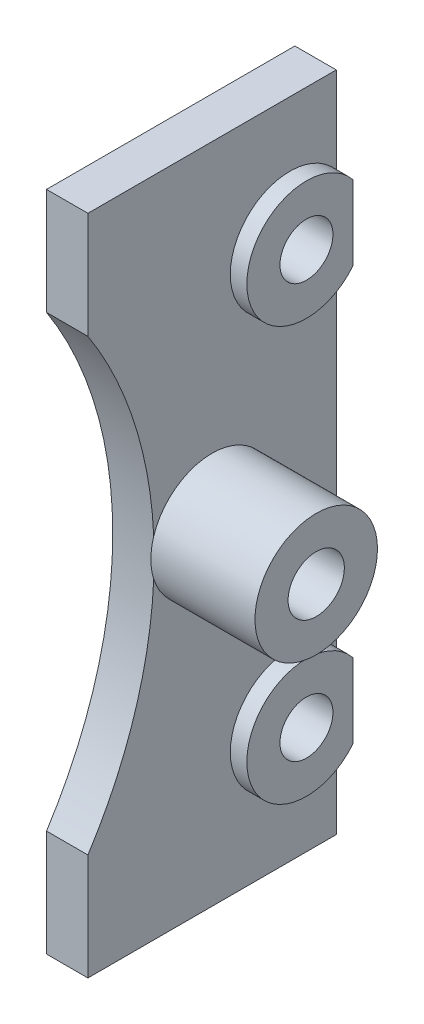
SolidWorks part; units mm, degrees
note: The reader was unsure of these and kept them because the rebuilt part matched: shared geometry of "Sketch1<3>".
ref_plane "Front" through (0, 0, 0) normal (0, 0, 1) x (1, 0, 0)
ref_plane "Top" through (0, 0, 0) normal (0, 1, 0) x (1, 0, 0)
ref_plane "Right" through (0, 0, 0) normal (1, 0, 0) x (0, 0, -1)
sketch "Sketch1" plane through (0, 0, 0) normal (1, 0, 0) x (0, 0, -1)
  line L0 (7.5, 40) -> (7.5, 0)
  line L1 (0, 0) -> (15, 0)
  line L2 (0, 0) -> (0, 40)
  line L3 (0, 40) -> (15, 40)
  line L4 (15, 0) -> (15, 40)
  line L5 (12.2, 29.2668) -> (15, 30.8834)
  line L6 (15, 30.8834) -> (15, 34.1166)
  line L7 (15, 34.1166) -> (12.2, 35.7332)
  line L8 (12.2, 35.7332) -> (9.4, 34.1166)
  line L9 (9.4, 34.1166) -> (9.4, 30.8834)
  line L10 (9.4, 30.8834) -> (12.2, 29.2668)
  line L11 (12.2, 4.2668) -> (15, 5.8834)
  line L12 (15, 5.8834) -> (15, 9.1166)
  line L13 (15, 9.1166) -> (12.2, 10.7332)
  line L14 (12.2, 10.7332) -> (9.4, 9.1166)
  line L15 (9.4, 9.1166) -> (9.4, 5.8834)
  line L16 (9.4, 5.8834) -> (12.2, 4.2668)
  circle A0 centre (12.2, 32.5) radius 2.8 construction
  circle A1 centre (12.2, 7.5) radius 2.8 construction
  circle A2 centre (7.5, 8) radius 1.6
  circle A3 centre (7.5, 20) radius 1.7
  circle A4 centre (12.2, 32.5) radius 1.6
  circle A5 centre (12.2, 7.5) radius 1.6
  dimension "D3" = 2.8
  dimension "D7" = 20
  dimension "D1" = 15
  dimension "D2" = 40
  dimension "D4" = 2.8
  dimension "D5" = 7.5
  dimension "D6" = 7.5
  dimension "D8" = 8
extrude "Boss-Extrude1" add sketch "Sketch1" along normal blind 2.5 contours A3 L0 L3 L2 L1 A2 | A3 L0 A2 L1 L4 L11 L16 L15 L14 L13 L5 L10 L9 L8 L7 L3 | L0 A2 | L0 A2 | L15 L16 L11 L4 L13 L14 A5 | L9 L10 L5 L4 L7 L8 A4
extrude "Boss-Extrude2" add sketch "Sketch1<3>" against normal blind 2.5 contours A3 L0 A2 L1 L4 L11 L16 L15 L14 L13 L5 L10 L9 L8 L7 L3 | A3 L0 L3 L2 L1 A2 | L15 L16 L11 L4 L13 L14 A5 | L9 L10 L5 L4 L7 L8 A4
sketch "Sketch1<3>" plane through (0, 0, 0) normal (1, 0, 0) x (0, 0, -1) same geometry as "Sketch1"
sketch "Sketch2" plane through (-2.5, 0, 0) normal (-1, 0, 0) x (0, 0, 1)
  line L0 (-15, 3.8462) -> (-15, 37.0094)
  line L1 (-15, 0) -> (-15, 40) construction
  circle A0 centre (-12.2, 7.5) radius 1.6
  circle A1 centre (-12.2, 32.5) radius 1.6
  circle A2 centre (-12.2, 7.5) radius 3.6
  circle A3 centre (-12.2, 32.5) radius 3.6
  circle M7 centre (-12.2, 32.5) radius 1.6
  circle M8 centre (-12.2, 7.5) radius 1.6
  dimension "D1" = 2
  dimension "D2" = 2
move or copy body "Body-Move/Copy1" bodies to move or copy 103
sketch "Sketch3" plane through (-2.5, 0, 0) normal (1, 0, 0) x (0, 0, -1)
  circle A0 centre (7.5, 20) radius 1.7
extrude "Extrude-Thin2" add sketch "Sketch3" along normal blind 6.29 thin
sketch "Sketch4" plane through (-7.5, 0, 0) normal (-1, 0, 0) x (0, 0, 1)
  line L1 (0, 0) -> (-15, 0)
  line L2 (0, 0) -> (0, 40)
  line L3 (0, 40) -> (-15, 40)
  line L4 (-15, 0) -> (-15, 40)
extrude "Cut-Extrude1" cut sketch "Sketch4" against normal blind 2.5
sketch "Sketch5" plane through (-5, 0, 0) normal (-1, 0, 0) x (0, 0, 1)
  line L0 (-7.5, 20) -> (21, 20)
  circle A0 centre (21, 20) radius 25
  line M5 (0, 0) -> (0, 40)
  dimension "D1" = 28.5
extrude "Cut-Extrude2" cut sketch "Sketch5" against normal blind 2.5 contours A0 L0 M5 | L0 A0 M5
extrude "Boss-Extrude3" add sketch "Sketch2" against normal blind 1 contours L0 A2 M8 | L0 A3 M7
